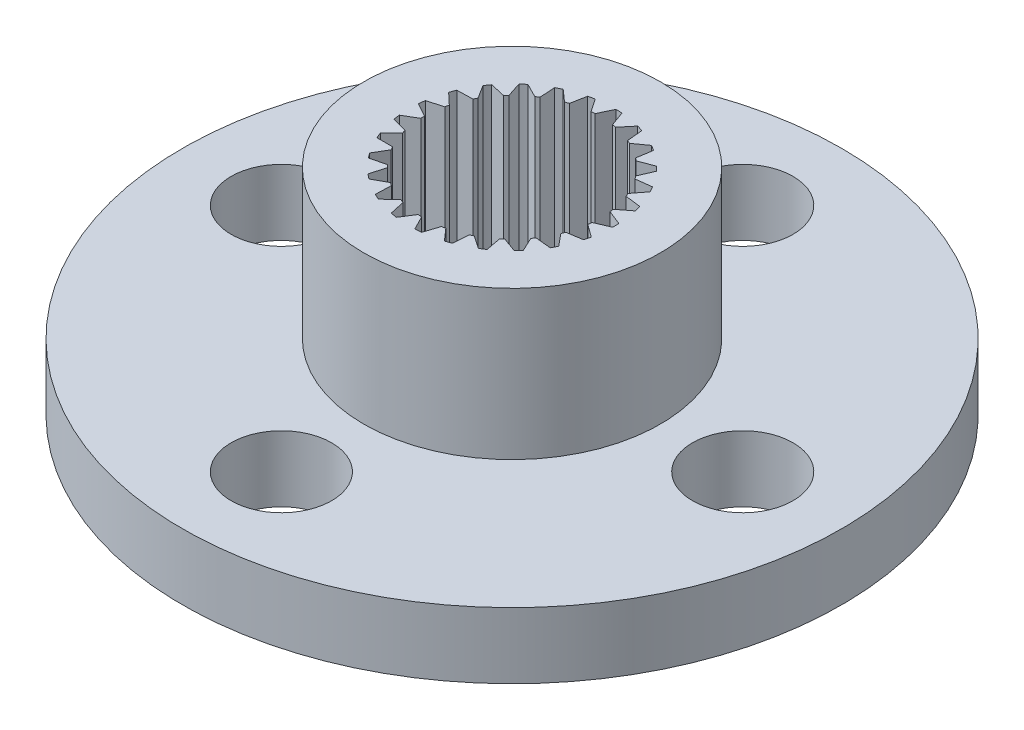
SolidWorks part; units mm, degrees
ref_plane "Front Plane" through (0, 0, 0) normal (0, 0, 1) x (1, 0, 0)
ref_plane "Top Plane" through (0, 0, 0) normal (0, 1, 0) x (1, 0, 0)
ref_plane "Right Plane" through (0, 0, 0) normal (1, 0, 0) x (0, 0, -1)
sketch "Sketch1" plane through (24.3015, 0, -59.2505) normal (0, -1, 0) x (0.9556, 0, 0.2946)
  line L0 (-1.3378, 2.3147) -> (-1.7435, 2.5633)
  line L1 (-1.8991, 2.4502) -> (-1.788, 1.9876)
  line L2 (-1.8714, 1.9093) -> (-2.3261, 2.0492)
  line L3 (-2.4487, 1.901) -> (-2.2261, 1.4805)
  line L4 (-2.2874, 1.3839) -> (-2.7627, 1.4063)
  line L5 (-2.8446, 1.2323) -> (-2.5244, 0.8804)
  line L6 (-2.5597, 0.7715) -> (-3.0256, 0.6751)
  line L7 (-3.0616, 0.4861) -> (-2.664, 0.2249)
  line L8 (-2.6712, 0.1107) -> (-3.0984, -0.0986)
  line L9 (-3.0864, -0.2905) -> (-2.6362, -0.4446)
  line L10 (-2.6148, -0.5571) -> (-2.9766, -0.866)
  line L11 (-2.9171, -1.0489) -> (-2.4428, -1.0863)
  line L12 (-2.3941, -1.1898) -> (-2.6677, -1.5791)
  line L13 (-2.5646, -1.7415) -> (-2.0959, -1.6597)
  line L14 (-2.023, -1.7478) -> (-2.1912, -2.1929)
  line L15 (-2.051, -2.3245) -> (-1.6174, -2.1288)
  line L16 (-1.5248, -2.196) -> (-1.577, -2.6689)
  line L17 (-1.4085, -2.7616) -> (-1.0371, -2.4641)
  line L18 (-0.9307, -2.5062) -> (-0.8637, -2.9772)
  line L19 (-0.6774, -3.0251) -> (-0.3918, -2.6446)
  line L20 (-0.2782, -2.659) -> (-0.0962, -3.0985)
  line L21 (0.0962, -3.0985) -> (0.2782, -2.659)
  line L22 (0.3918, -2.6446) -> (0.6774, -3.0251)
  line L23 (0.8637, -2.9772) -> (0.9307, -2.5062)
  line L24 (1.0371, -2.4641) -> (1.4085, -2.7616)
  line L25 (1.577, -2.6689) -> (1.5248, -2.196)
  line L26 (1.6174, -2.1288) -> (2.051, -2.3245)
  line L27 (2.1912, -2.1929) -> (2.023, -1.7478)
  line L28 (2.0959, -1.6597) -> (2.5646, -1.7415)
  line L29 (2.6677, -1.5791) -> (2.3941, -1.1898)
  line L30 (2.4428, -1.0863) -> (2.9171, -1.0489)
  line L31 (2.9766, -0.866) -> (2.6148, -0.5571)
  line L32 (2.6362, -0.4446) -> (3.0864, -0.2905)
  line L33 (3.0984, -0.0986) -> (2.6712, 0.1107)
  line L34 (2.664, 0.2249) -> (3.0616, 0.4861)
  line L35 (3.0256, 0.6751) -> (2.5597, 0.7715)
  line L36 (2.5244, 0.8804) -> (2.8446, 1.2323)
  line L37 (2.7627, 1.4063) -> (2.2874, 1.3839)
  line L38 (2.2261, 1.4805) -> (2.4487, 1.901)
  line L39 (2.3261, 2.0492) -> (1.8714, 1.9093)
  line L40 (1.788, 1.9876) -> (1.8991, 2.4502)
  line L41 (1.7435, 2.5633) -> (1.3378, 2.3147)
  line L42 (1.2375, 2.3698) -> (1.23, 2.8455)
  line L43 (1.0512, 2.9163) -> (0.7201, 2.5747)
  line L44 (0.6093, 2.6031) -> (0.4837, 3.062)
  line L45 (0.2929, 3.0861) -> (0.0572, 2.6729)
  line L46 (-0.0572, 2.6729) -> (-0.2929, 3.0861)
  line L47 (-0.4837, 3.062) -> (-0.6093, 2.6031)
  line L48 (-0.7201, 2.5747) -> (-1.0512, 2.9163)
  line L49 (-1.23, 2.8455) -> (-1.2375, 2.3698)
  line L200 (-1.8428, 2.4303) -> (-1.7394, 1.9993) construction
  line L201 (-1.3639, 2.272) -> (-1.7419, 2.5037) construction
  line L202 (-1.8861, 1.8615) -> (-2.3098, 1.9918) construction
  line L203 (-2.3893, 1.8957) -> (-2.1819, 1.5039) construction
  line L204 (-2.2898, 1.3339) -> (-2.7326, 1.3548) construction
  line L205 (-2.7857, 1.2419) -> (-2.4874, 0.914) construction
  line L206 (-3.007, 0.5101) -> (-2.6365, 0.2667) construction
  line L207 (-2.5496, 0.7226) -> (-2.9837, 0.6327) construction
  line L208 (-3.0394, -0.2537) -> (-2.62, -0.3973) construction
  line L209 (-2.6492, 0.0658) -> (-3.0473, -0.1292) construction
  line L210 (-2.8808, -1.0016) -> (-2.4389, -1.0364) construction
  line L211 (-2.5823, -0.5951) -> (-2.9194, -0.883) construction
  line L212 (-2.5412, -1.6866) -> (-2.1045, -1.6104) construction
  line L213 (-2.3532, -1.2186) -> (-2.6081, -1.5812) construction
  line L214 (-2.0419, -2.2656) -> (-1.6379, -2.0832) construction
  line L215 (-1.9762, -1.7655) -> (-2.1329, -2.1802) construction
  line L216 (-1.4144, -2.7022) -> (-1.0684, -2.4251) construction
  line L217 (-1.4751, -2.2015) -> (-1.5237, -2.6421) construction
  line L218 (-0.6979, -2.9691) -> (-0.4318, -2.6146) construction
  line L219 (-0.8812, -2.4992) -> (-0.8188, -2.938) construction
  line L220 (0.0624, -3.0494) -> (0.232, -2.6398) construction
  line L221 (-0.232, -2.6398) -> (-0.0624, -3.0494) construction
  line L222 (0.8188, -2.938) -> (0.8812, -2.4992) construction
  line L223 (0.4318, -2.6146) -> (0.6979, -2.9691) construction
  line L224 (1.0684, -2.4251) -> (1.4144, -2.7022) construction
  line L225 (1.5237, -2.6421) -> (1.4751, -2.2015) construction
  line L226 (1.6379, -2.0832) -> (2.0419, -2.2656) construction
  line L227 (2.1329, -2.1802) -> (1.9762, -1.7655) construction
  line L228 (2.1045, -1.6104) -> (2.5412, -1.6866) construction
  line L229 (2.6081, -1.5812) -> (2.3532, -1.2186) construction
  line L230 (2.4389, -1.0364) -> (2.8808, -1.0016) construction
  line L231 (2.9194, -0.883) -> (2.5823, -0.5951) construction
  line L232 (3.0473, -0.1292) -> (2.6492, 0.0658) construction
  line L233 (2.62, -0.3973) -> (3.0394, -0.2537) construction
  line L234 (2.9837, 0.6327) -> (2.5496, 0.7226) construction
  line L235 (2.6365, 0.2667) -> (3.007, 0.5101) construction
  line L236 (2.7326, 1.3548) -> (2.2898, 1.3339) construction
  line L237 (2.4874, 0.914) -> (2.7857, 1.2419) construction
  line L238 (2.3098, 1.9918) -> (1.8861, 1.8615) construction
  line L239 (2.1819, 1.5039) -> (2.3893, 1.8957) construction
  line L240 (1.7394, 1.9993) -> (1.8428, 2.4303) construction
  line L241 (1.7419, 2.5037) -> (1.3639, 2.272) construction
  line L242 (1.0645, 2.8582) -> (0.756, 2.5399) construction
  line L243 (1.1875, 2.369) -> (1.1806, 2.8123) construction
  line L244 (0.5611, 2.5899) -> (0.4441, 3.0175) construction
  line L245 (0.3203, 3.0331) -> (0.1007, 2.6481) construction
  line L246 (-0.4441, 3.0175) -> (-0.5611, 2.5899) construction
  line L247 (-0.1007, 2.6481) -> (-0.3203, 3.0331) construction
  line L248 (-1.1806, 2.8123) -> (-1.1875, 2.369) construction
  line L249 (-0.756, 2.5399) -> (-1.0645, 2.8582) construction
  arc A0 (-1.7435, 2.5633) -> (-1.8991, 2.4502) centre (0, 0) ccw
  arc A1 (-2.3261, 2.0492) -> (-2.4487, 1.901) centre (0, 0) ccw
  arc A2 (-2.7627, 1.4063) -> (-2.8446, 1.2323) centre (0, 0) ccw
  arc A3 (-3.0256, 0.6751) -> (-3.0616, 0.4861) centre (0, 0) ccw
  arc A4 (-3.0984, -0.0986) -> (-3.0864, -0.2905) centre (0, 0) ccw
  arc A5 (-2.9766, -0.866) -> (-2.9171, -1.0489) centre (0, 0) ccw
  arc A6 (-2.6677, -1.5791) -> (-2.5646, -1.7415) centre (0, 0) ccw
  arc A7 (-2.1912, -2.1929) -> (-2.051, -2.3245) centre (0, 0) ccw
  arc A8 (-1.577, -2.6689) -> (-1.4085, -2.7616) centre (0, 0) ccw
  arc A9 (-0.8637, -2.9772) -> (-0.6774, -3.0251) centre (0, 0) ccw
  arc A10 (-0.0962, -3.0985) -> (0.0962, -3.0985) centre (0, 0) ccw
  arc A11 (0.6774, -3.0251) -> (0.8637, -2.9772) centre (0, 0) ccw
  arc A12 (1.4085, -2.7616) -> (1.577, -2.6689) centre (0, 0) ccw
  arc A13 (2.051, -2.3245) -> (2.1912, -2.1929) centre (0, 0) ccw
  arc A14 (2.5646, -1.7415) -> (2.6677, -1.5791) centre (0, 0) ccw
  arc A15 (2.9171, -1.0489) -> (2.9766, -0.866) centre (0, 0) ccw
  arc A16 (3.0864, -0.2905) -> (3.0984, -0.0986) centre (0, 0) ccw
  arc A17 (3.0616, 0.4861) -> (3.0256, 0.6751) centre (0, 0) ccw
  arc A18 (2.8446, 1.2323) -> (2.7627, 1.4063) centre (0, 0) ccw
  arc A19 (2.4487, 1.901) -> (2.3261, 2.0492) centre (0, 0) ccw
  arc A20 (1.8991, 2.4502) -> (1.7435, 2.5633) centre (0, 0) ccw
  arc A21 (1.23, 2.8455) -> (1.0512, 2.9163) centre (0, 0) ccw
  arc A22 (0.4837, 3.062) -> (0.2929, 3.0861) centre (0, 0) ccw
  arc A23 (-0.2929, 3.0861) -> (-0.4837, 3.062) centre (0, 0) ccw
  arc A24 (-1.0512, 2.9163) -> (-1.23, 2.8455) centre (0, 0) ccw
  circle A25 centre (0, 0) radius 2.6735
  circle A152 centre (0, 0) radius 4.5
  arc A205 (-1.7419, 2.5037) -> (-1.8428, 2.4303) centre (0, 0) ccw construction
  arc A206 (-2.3098, 1.9918) -> (-2.3893, 1.8957) centre (0, 0) ccw construction
  arc A208 (-2.7326, 1.3548) -> (-2.7857, 1.2419) centre (0, 0) ccw construction
  arc A211 (-2.9837, 0.6327) -> (-3.007, 0.5101) centre (0, 0) ccw construction
  arc A213 (-3.0473, -0.1292) -> (-3.0394, -0.2537) centre (0, 0) ccw construction
  arc A215 (-2.9194, -0.883) -> (-2.8808, -1.0016) centre (0, 0) ccw construction
  arc A217 (-2.6081, -1.5812) -> (-2.5412, -1.6866) centre (0, 0) ccw construction
  arc A219 (-2.1329, -2.1802) -> (-2.0419, -2.2656) centre (0, 0) ccw construction
  arc A221 (-1.5237, -2.6421) -> (-1.4144, -2.7022) centre (0, 0) ccw construction
  arc A223 (-0.8188, -2.938) -> (-0.6979, -2.9691) centre (0, 0) ccw construction
  arc A225 (-0.0624, -3.0494) -> (0.0624, -3.0494) centre (0, 0) ccw construction
  arc A227 (0.6979, -2.9691) -> (0.8188, -2.938) centre (0, 0) ccw construction
  arc A228 (1.4144, -2.7022) -> (1.5237, -2.6421) centre (0, 0) ccw construction
  arc A230 (2.0419, -2.2656) -> (2.1329, -2.1802) centre (0, 0) ccw construction
  arc A232 (2.5412, -1.6866) -> (2.6081, -1.5812) centre (0, 0) ccw construction
  arc A234 (2.8808, -1.0016) -> (2.9194, -0.883) centre (0, 0) ccw construction
  arc A237 (3.0394, -0.2537) -> (3.0473, -0.1292) centre (0, 0) ccw construction
  arc A239 (3.007, 0.5101) -> (2.9837, 0.6327) centre (0, 0) ccw construction
  arc A241 (2.7857, 1.2419) -> (2.7326, 1.3548) centre (0, 0) ccw construction
  arc A243 (2.3893, 1.8957) -> (2.3098, 1.9918) centre (0, 0) ccw construction
  arc A244 (1.8428, 2.4303) -> (1.7419, 2.5037) centre (0, 0) ccw construction
  arc A247 (1.1806, 2.8123) -> (1.0645, 2.8582) centre (0, 0) ccw construction
  arc A248 (0.4441, 3.0175) -> (0.3203, 3.0331) centre (0, 0) ccw construction
  arc A251 (-0.3203, 3.0331) -> (-0.4441, 3.0175) centre (0, 0) ccw construction
  arc A253 (-1.0645, 2.8582) -> (-1.1806, 2.8123) centre (0, 0) ccw construction
  dimension "D2" = 9
  dimension "D1" = 0.05
extrude "Boss-Extrude1" add sketch "Sketch1" against normal blind 6.5 contours A152 L43 A25 L44 A22 L45 L46 A23 L47 L48 A24 L49 L0 A0 L1 L2 A1 L3 L4 A2 L5 L6 A3 L7 L8 A4 L9 L10 A5 L11 L12 A6 L13 L14 A7 L15 L16 A8 L17 region at (20.1228, 0, -60.5386)
sketch "Sketch2" plane through (0, 0, 0) normal (0, -1, 0) x (-1, 0, 0)
  circle A0 centre (-24.3015, 59.2505) radius 10
  dimension "D1" = 20
extrude "Boss-Extrude2" add sketch "Sketch2" against normal blind 2
sketch "Sketch3" plane through (0, 0, 0) normal (0, -1, 0) x (-1, 0, 0)
  circle A6 centre (-24.3015, 66.2505) radius 1.525
  circle A8 centre (-17.3015, 59.2505) radius 1.525
  circle A9 centre (-24.3015, 52.2505) radius 1.525
  circle A10 centre (-31.3015, 59.2505) radius 1.525
  circle A13 centre (-24.3015, 59.2505) radius 10
  circle A14 centre (-24.3015, 59.2505) radius 10 construction
  point P2 (0, 0)
  point P3 (0, 0)
  point P4 (0, 0)
  point P5 (0, 0)
  point P8 (0, 0)
  point P10 (0, 0)
  point P17 (-24.3015, 59.2505)
  point P18 (-24.3015, 59.2505)
  point P20 (0, 0)
  point P21 (0, 0)
  point P22 (-26.3486, 58.2821)
  dimension "D1" = 3.05
  dimension "D4" = 14
  dimension "D2" = 4
  dimension "D3" = 0
extrude "Cut-Extrude1" cut sketch "Sketch3" against normal through all
